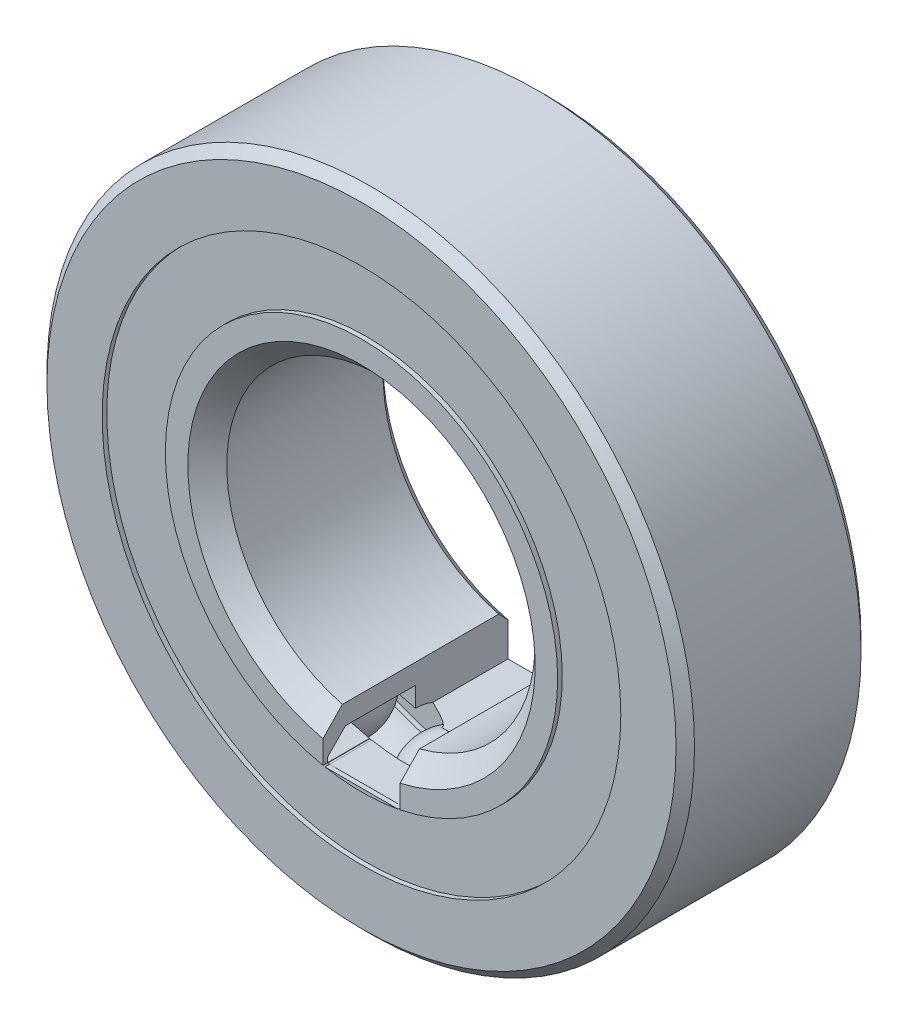
SolidWorks part; units mm, degrees
ref_plane "Front Plane" through (0, 0, 0) normal (0, 0, 1) x (1, 0, 0)
ref_plane "Top Plane" through (0, 0, 0) normal (0, 1, 0) x (1, 0, 0)
ref_plane "Right Plane" through (0, 0, 0) normal (1, 0, 0) x (0, 0, -1)
sketch "Sketch1" plane through (0, 0, 0) normal (1, 0, 0) x (0, 0, -1)
  line L0 (-6, 0) -> (6, 0) construction
  line L1 (0, 21) -> (0, -21) construction
  line L2 (5.4, 21) -> (-5.4, 21)
  line L3 (-5.4, 21) -> (-6, 20.4)
  line L4 (-6, 20.4) -> (-6, 16.8187)
  line L5 (-6, 16.8187) -> (-2.6667, 16.8187)
  line L6 (6, 16.8187) -> (2.6667, 16.8187)
  line L7 (6, 20.4) -> (6, 16.8187)
  line L8 (5.4, 21) -> (6, 20.4)
  line L9 (0, 21) -> (0, 15.5) construction
  line L10 (0, 15.5) -> (0, 10) construction
  arc A0 (-2.6667, 16.8187) -> (2.6667, 16.8187) centre (0, 15.5) cw
  point P14 (0, 10)
  dimension "Width" = 12
  dimension "OD" = 42
  dimension "D1" = 45
  dimension "D2" = 0.6
  dimension "D3" = 5.3333
  dimension "D4" = 1.3187
revolve "Revolve1" add sketch "Sketch1" angle 360 about L0
sketch "Sketch2" plane through (0, 0, 0) normal (1, 0, 0) x (0, 0, -1)
  line L0 (-5.7, 14.1813) -> (-2.6667, 14.1813)
  line L1 (-6, 20.4) -> (-6, -20.4) construction
  line L2 (-6, 12.7219) -> (-5.7, 12.7219) construction
  line L3 (-5.7, 12.4219) -> (-4.5406, 11.2625)
  line L4 (-4.5406, 11.2625) -> (0, 11.2625)
  line L5 (0, 21) -> (0, -21) construction
  line L6 (0, 11.2625) -> (0, 12.5251)
  line L7 (0, 12.5251) -> (0, 10) construction
  line L8 (-6, 14.1813) -> (-6, 11.2625) construction
  line L9 (-6, 11.2625) -> (-4.5406, 11.2625) construction
  line L10 (-5.7, 14.1813) -> (-5.7, 12.4219)
  line L11 (-5.7, 14.1813) -> (-5.7, 20.7) construction
  line L12 (-5.4, 21) -> (-6, 20.4) construction
  arc A0 (-2.6667, 14.1813) -> (0, 12.5251) centre (0, 15.5) ccw
  arc A1 (2.6667, 16.8187) -> (-2.6667, 16.8187) centre (0, 15.5) ccw construction
  circle A2 centre (0, 15.5) radius 2.9749 construction
  dimension "D1" = 45
revolve "Revolve2" [suppressed] add sketch "Sketch2" angle 360 about L0
sketch "Sketch3" plane through (0, 0, 0) normal (1, 0, 0) x (0, 0, -1)
  line L0 (-5.7, 12.4219) -> (-4.5406, 11.2625)
  line L1 (-4.5406, 11.2625) -> (0, 11.2625)
  line L2 (0, 11.2625) -> (0, 12.5251)
  line L3 (-6, 12.7219) -> (-6, 11.2625)
  line L4 (-6, 14.1813) -> (-6, 11.2625) construction
  line L5 (-6, 11.2625) -> (-4.7375, 10)
  line L6 (-4.7375, 10) -> (5.4, 10)
  line L7 (5.4, 21) -> (5.4, -21) construction
  line L8 (5.4, 10) -> (6, 10.6)
  line L9 (6, -20.4) -> (6, 20.4) construction
  line L10 (6, 10.6) -> (6, 14.1813)
  line L11 (6, 14.1813) -> (2.6667, 14.1813)
  line L12 (-6, 12.7219) -> (-5.7, 12.7219)
  line L13 (5.4, 21) -> (6, 20.4) construction
  line L14 (-5.7, 12.7219) -> (-5.7, 12.4219)
  circle A0 centre (0, 15.5) radius 2.9749 construction
  arc A1 (2.6667, 14.1813) -> (0, 12.5251) centre (0, 15.5) cw
revolve "Revolve3" add sketch "Sketch3" angle 360 about L0
sketch "Sketch4" plane through (0, 0, 0) normal (1, 0, 0) x (0, 0, -1)
  line L0 (-2.9749, 15.5) -> (2.9749, 15.5)
  circle A1 centre (0, 15.5) radius 2.9749 construction
  arc A2 (-2.9749, 15.5) -> (2.9749, 15.5) centre (0, 15.5) cw
  arc A3 (2.6667, 16.8187) -> (-2.6667, 16.8187) centre (0, 15.5) ccw construction
revolve "Revolve4" add sketch "Sketch4" angle 360 about L0 other way angle 360
ref_axis "Axis1" through (0, 0, -6) along (0, 0, 1)
pattern_circular "CirPattern1" count 12 over 360 about axis through (0, 0, -6) along (0, 0, 1) of bodies 104
sketch "Sketch5" plane through (0, 0, 0) normal (1, 0, 0) x (0, 0, -1)
  line L0 (-6, 16.8187) -> (-2.6667, 16.8187) construction
  line L1 (-5.7, 16.8187) -> (-2.9749, 16.8187)
  line L2 (-5.7, 16.8187) -> (-5.7, 12.7219)
  line L3 (-5.7, 12.7219) -> (-2.9749, 12.7219)
  line L4 (-2.9749, 16.8187) -> (-2.9749, 12.7219)
  line L6 (-5.4, 21) -> (-6, 20.4) construction
  line L7 (0, 21) -> (0, 10) construction
  line L8 (5.7, 12.7219) -> (2.9749, 12.7219)
  line L9 (2.9749, 16.8187) -> (2.9749, 12.7219)
  line L10 (5.7, 16.8187) -> (2.9749, 16.8187)
  line L11 (5.7, 16.8187) -> (5.7, 12.7219)
  circle A0 centre (0, 15.5) radius 2.9749 construction
  point P10 (-5.7, 20.7)
revolve "Revolve5" add sketch "Sketch5" angle 360 about L0
sketch "Sketch6" plane through (0, 0, 6) normal (0, 0, 1) x (1, 0, 0)
  line L0 (0, 0) -> (0, -22.9851) construction
  line L2 (-2.5, -12.5) -> (2.5, -12.5)
  line L3 (-2.5, -12.5) -> (-2.5, -7.5)
  line L4 (-2.5, -7.5) -> (2.5, -7.5)
  line L5 (2.5, -12.5) -> (2.5, -7.5)
  line L6 (-2.5, -12.5) -> (2.5, -7.5) construction
  line L7 (-2.5, -7.5) -> (2.5, -12.5) construction
  circle A2 centre (0, 0) radius 11.2625 construction
  point P4 (0, -10)
  dimension "D1" = 7.5
  dimension "D3" = 5
extrude "Cut-Extrude1" cut sketch "Sketch6" against normal through all
equation "\"D2@Sketch1\" = \"Width@Sketch1\"*.05"
equation "\"D3@Sketch1\" = \"Width@Sketch1\"/2.25"
equation "\"D4@Sketch1\" = (((\"OD@Sketch1\"-\"Width@Sketch1\")/2)/3.25)/3.5"
equation "\"D2@CirPattern1\" = 360/\"Balls@CirPattern1\""
